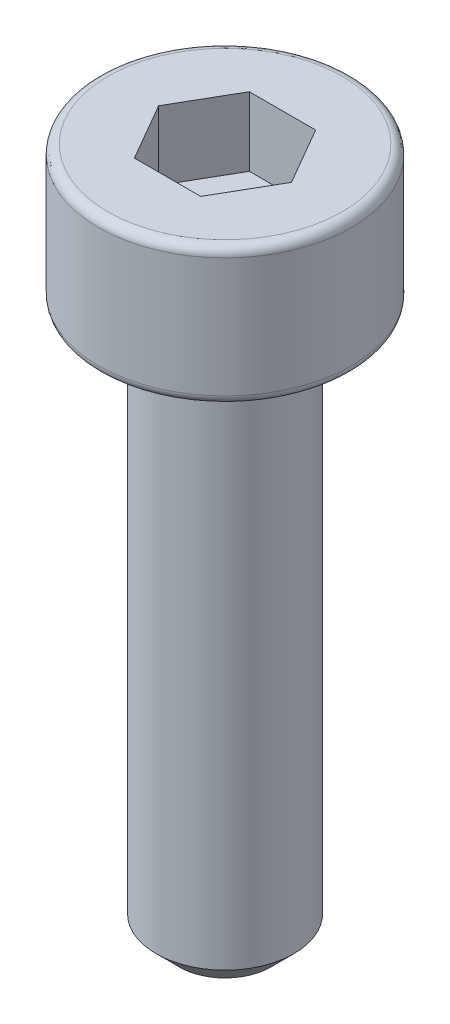
SolidWorks part; units mm, degrees
ref_plane "Front Plane" through (0, 0, 0) normal (0, 0, 1) x (1, 0, 0)
ref_plane "Top Plane" through (0, 0, 0) normal (0, 1, 0) x (1, 0, 0)
ref_plane "Right Plane" through (0, 0, 0) normal (1, 0, 0) x (0, 0, -1)
sketch "Sketch1" plane through (0, 0, 0) normal (0, 1, 0) x (1, 0, 0)
  circle A0 centre (0, 0) radius 2.75
  dimension "D1" = 5.5
extrude "Boss-Extrude1" add sketch "Sketch1" against normal blind 3
sketch "Sketch2" plane through (0, 0, 0) normal (0, 1, 0) x (1, 0, 0)
  line L1 (1.4434, 0) -> (0.7217, 1.25)
  line L2 (0.7217, 1.25) -> (-0.7217, 1.25)
  line L3 (-0.7217, 1.25) -> (-1.4434, 0)
  line L4 (-1.4434, 0) -> (-0.7217, -1.25)
  line L5 (-0.7217, -1.25) -> (0.7217, -1.25)
  line L6 (0.7217, -1.25) -> (1.4434, 0)
  circle A0 centre (0, 0) radius 1.25 construction
  dimension "D1" = 2.5
extrude "Cut-Extrude1" cut sketch "Sketch2" against normal blind 1.5
sketch "Sketch3" plane through (0, -3, 0) normal (0, -1, 0) x (1, 0, 0)
  circle A0 centre (0, 0) radius 1.5
  dimension "D1" = 3
extrude "Boss-Extrude2" add sketch "Sketch3" along normal blind 0.0001
sketch "Sketch4" plane through (0, -3.0001, 0) normal (0, -1, 0) x (1, 0, 0)
  circle A0 centre (0, 0) radius 1.5
  circle A1 centre (0, 0) radius 1.5 construction
extrude "Boss-Extrude3" add sketch "Sketch4" along normal blind 12 separate body
chamfer "Chamfer1" distance 0.5 angle 45 1 edges at (0, -15.0001, -1.5)
fillet "Fillet1" radius 0.2 2 edges at (0, -3, 2.75) (0, 0, 2.75)
